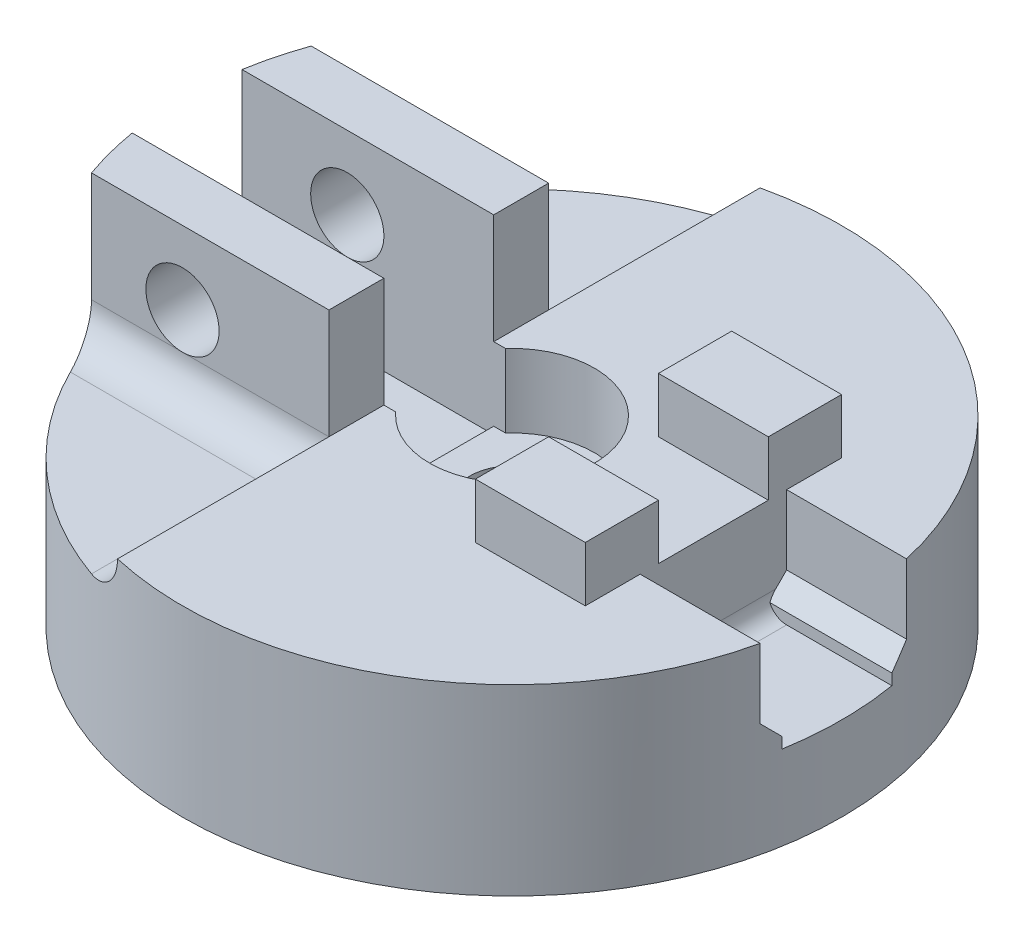
SolidWorks part; units mm, degrees
ref_plane "Front Plane" through (0, 0, 0) normal (0, 0, 1) x (1, 0, 0)
ref_plane "Top Plane" through (0, 0, 0) normal (0, 1, 0) x (1, 0, 0)
ref_plane "Right Plane" through (0, 0, 0) normal (1, 0, 0) x (0, 0, -1)
sketch "Sketch1" plane through (0, 0, 0) normal (0, 1, 0) x (1, 0, 0)
  circle A0 centre (0, 0) radius 9
  dimension "D1" = 18
extrude "Boss-Extrude1" add sketch "Sketch1" along normal blind 8
sketch "Sketch2" plane through (0, 8, 0) normal (0, 1, 0) x (1, 0, 0)
  circle A0 centre (0, 0) radius 1.15
  dimension "D1" = 2.3
extrude "Cut-Extrude1" cut sketch "Sketch2" against normal through all
sketch "Sketch5" plane through (0, 8, 0) normal (0, 1, 0) x (1, 0, 0)
  line L1 (-2, 3) -> (-8.4853, 3)
  line L2 (-2, 3) -> (-2, 8.775)
  line L3 (-2, 8.775) -> (-8.4853, 8.775)
  line L4 (-8.4853, 3) -> (-8.4853, 8.775)
  circle A2 centre (0, 0) radius 9 construction
  dimension "D1" = 2
  dimension "D2" = 3
extrude "Cut-Extrude3" cut sketch "Sketch5" against normal blind 4
mirror "Mirror1" about plane through (0, 0, 0) normal (0, 0, 1) of "Cut-Extrude3"
sketch "Sketch6" plane through (0, 8, 0) normal (0, 1, 0) x (1, 0, 0)
  line L0 (-2, -3) -> (-2, -8.775) construction
  line L1 (-2, 9) -> (23.0525, 9)
  line L2 (-2, 9) -> (-2, -20.0526)
  line L3 (-2, -20.0526) -> (23.0525, -20.0526)
  line L4 (23.0525, 9) -> (23.0525, -20.0526)
  arc A0 (-2, -8.775) -> (-2, 8.775) centre (0, 0) ccw construction
extrude "Cut-Extrude4" cut sketch "Sketch6" against normal blind 3
sketch "Sketch7" plane through (0, 8, 0) normal (0, 1, 0) x (1, 0, 0)
  line L0 (-2, 3) -> (-2, -3) construction
  line L1 (-2, -1.5) -> (-12.173, -1.5)
  line L2 (-2, -1.5) -> (-2, 1.5)
  line L3 (-2, 1.5) -> (-12.173, 1.5)
  line L4 (-12.173, -1.5) -> (-12.173, 1.5)
  dimension "D1" = 1.5
  dimension "D2" = 3
extrude "Cut-Extrude5" cut sketch "Sketch7" against normal blind 5.2
sketch "Sketch10" plane through (0, 5, 0) normal (0, 1, 0) x (1, 0, 0)
  circle A0 centre (0, 0) radius 2.25
  dimension "D1" = 4.5
extrude "Cut-Extrude6" cut sketch "Sketch10" against normal blind 2
sketch "Sketch11" plane through (0, 0, 0) normal (0, -1, 0) x (1, 0, 0)
  circle A0 centre (0, 0) radius 6
  dimension "D1" = 12
extrude "Cut-Extrude7" cut sketch "Sketch11" against normal blind 2
sketch "Sketch12" plane through (0, 5, 0) normal (0, 1, 0) x (1, 0, 0)
  line L1 (5.5, -2) -> (11.6408, -2)
  line L2 (5.5, -2) -> (5.5, 2)
  line L3 (5.5, 2) -> (11.6408, 2)
  line L4 (11.6408, -2) -> (11.6408, 2)
  arc A0 (-2, -8.775) -> (-2, 8.775) centre (0, 0) ccw construction
  dimension "D1" = 5.5
  dimension "D2" = 2
  dimension "D3" = 2
extrude "Cut-Extrude8" cut sketch "Sketch12" against normal blind 2.7
sketch "Sketch13" plane through (0, 5, 0) normal (0, 1, 0) x (1, 0, 0)
  line L1 (-2, -1.5) -> (-1.15, -1.5)
  line L2 (-2, -1.5) -> (-2, 1.5)
  line L3 (-2, 1.5) -> (-1.15, 1.5)
  line L4 (-1.15, -1.5) -> (-1.15, 1.5)
  circle A0 centre (0, 0) radius 1.15 construction
extrude "Cut-Extrude9" cut sketch "Sketch13" against normal up to surface (2 mm away) up to face at (0.125, 3, 0)
hole_wizard "Ø2.0 (2) Diameter Hole1" positions "Sketch8" profile "Sketch9" hole size "Ø2.0" standard "DIN" end condition through all
sketch "Sketch8" plane through (0, 0, -3) normal (0, 0, -1) x (-1, 0, 0)
  line L0 (8.4853, 8) -> (2, 8) construction
  point P0 (6, 6)
  dimension "D1" = 2
  dimension "D2" = 6
sketch "Sketch9" plane through (-6, 6, -3) normal (1, 0, 0) x (0, 1, 0)
  line L0 (0, 0) -> (0, 12)
  line L1 (0, 12) -> (1, 12)
  line L2 (1, 12) -> (1, 0)
  line L5 (1, 0) -> (0, 0)
  line L11 (0, -6.35) -> (0, 107.95) construction
  dimension "Thru Hole Dia." = 2
  dimension "Thru Hole Depth" = 12
fillet "Fillet1" radius 2 1 edges at (0, 2, -6) type face fillet first side face at (0, 2, -6) second side face at (0, 2, -6)
fillet "Fillet2" radius 0.1 1 edges at (-2, 2.8, 0) type face fillet first side face at (-2, 2.9, 0) second side face at (-5.4685, 2.8, 0)
fillet "Fillet4" radius 1 2 edges at (-2, 4, -5.8875) (-5.2426, 4, -3) type face fillet first side face at (-4.4093, 4, -5.203) second side face at (-2, 4.5, -5.8875) second side face at (-7, 6, -3)
fillet "Fillet5" radius 1 2 edges at (-2, 4, 5.8875) (-5.2426, 4, 3) type face fillet first side face at (-4.4093, 4, 5.203) second side face at (-2, 4.5, 5.8875) second side face at (-5, 6, 3)
sketch "Sketch14" plane through (5.5, 0, 0) normal (1, 0, 0) x (0, 0, -1)
  line L5 (1.5, 2.3) -> (1.5, 2.6)
  line L6 (2, 2.3) -> (-2, 2.3) construction
  line L7 (1.5, 2.6) -> (2, 3.1)
  line L8 (2, 2.3) -> (2, 5) construction
  line L9 (2, 3.1) -> (2, 2.3)
  line L10 (2, 2.3) -> (1.5, 2.3)
  dimension "D1" = 0.3
  dimension "D2" = 0.5
  dimension "D3" = 0.8
extrude "Boss-Extrude2" add sketch "Sketch14" along normal up to surface (3.275 mm away) up to face at (-3.2382, 4.8602, 0.0097)
sketch "Sketch15" plane through (0, 5, 0) normal (0, 1, 0) x (1, 0, 0)
  line L0 (-2, 1.5) -> (-8.8741, 1.5) construction
  line L1 (5.5, 1.5) -> (2.5, 1.5)
  line L2 (5.5, 1.5) -> (5.5, 3.5)
  line L3 (5.5, 3.5) -> (2.5, 3.5)
  line L4 (2.5, 1.5) -> (2.5, 3.5)
  line L5 (5.5, 2) -> (5.5, -2) construction
  dimension "D1" = 3
  dimension "D2" = 2
extrude "Boss-Extrude3" add sketch "Sketch15" along normal blind 1.5
mirror "Mirror2" about plane through (0, 0, 0) normal (0, 0, 1) of "Boss-Extrude3", "Boss-Extrude2"
fillet "Fillet6" radius 0.5 1 edges at (5.5, 2.3, 0) type face fillet first side face at (5.5, 4.5, 0) second side face at (7.2185, 2.3, 0)
equation "\"D2@Sketch7\"=\"D1@Sketch7\"*2"
equation "\"D3@Sketch12\"=\"D2@Sketch12\""
equation "\"D3@Sketch14\"=\"D2@Sketch14\"+\"D1@Sketch14\""
